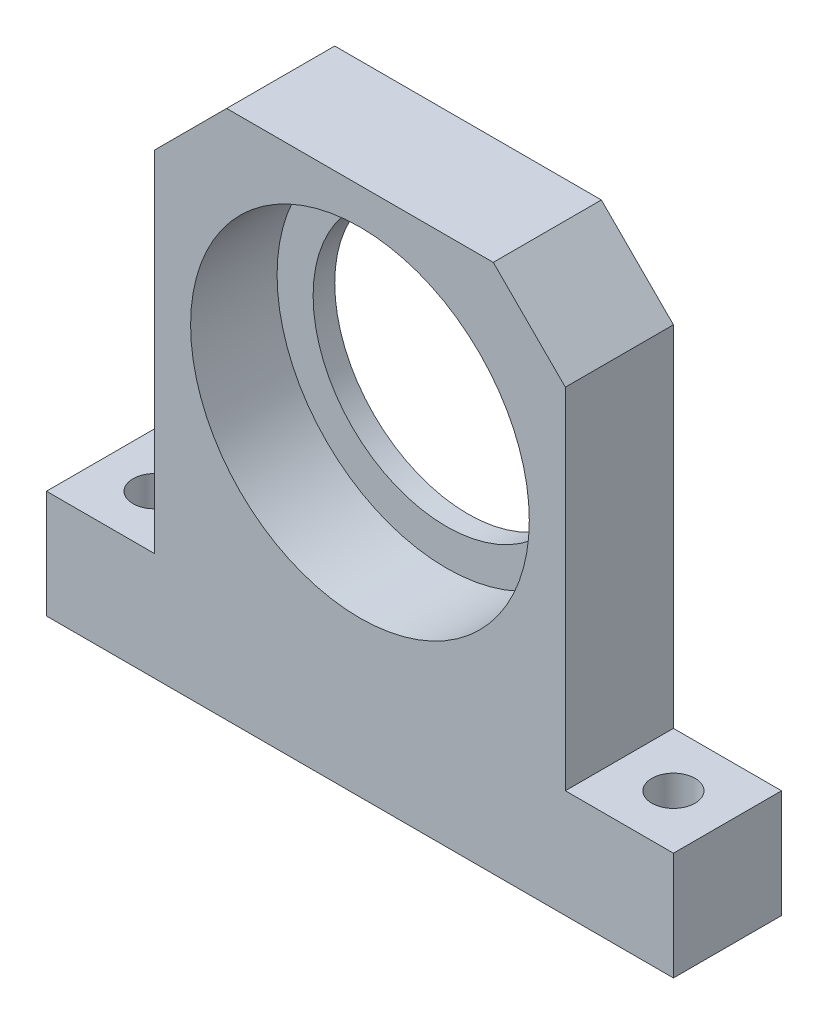
SolidWorks part; units mm, degrees
material "1060 合金"
ref_plane "前视" through (0, 0, 0) normal (0, 0, 1) x (1, 0, 0)
ref_plane "上视" through (0, 0, 0) normal (0, 1, 0) x (1, 0, 0)
ref_plane "右视" through (0, 0, 0) normal (1, 0, 0) x (0, 0, -1)
sketch "草图1" plane through (0, 0, 0) normal (0, 0, 1) x (1, 0, 0)
  line L0 (-28.5, 18.5) -> (-28.5, -30)
  line L1 (-28.5, -30) -> (-43.5, -30)
  line L2 (-43.5, -30) -> (-43.5, -45)
  line L3 (-43.5, -45) -> (43.5, -45)
  line L4 (43.5, -45) -> (43.5, -30)
  line L5 (43.5, -30) -> (28.5, -30)
  line L6 (28.5, -30) -> (28.5, 18.5)
  line L7 (18.5, 28.5) -> (-18.5, 28.5)
  line L8 (-18.5, 28.5) -> (-28.5, 18.5)
  line L9 (28.5, 18.5) -> (18.5, 28.5)
  circle A0 centre (0, 0) radius 23.5
  circle A1 centre (0, 0) radius 18.5
  point P10 (28.5, 28.5)
  point P11 (-28.5, 28.5)
  dimension "D1" = 47
  dimension "D14" = 5
  dimension "D2" = 28.5
  dimension "D3" = 28.5
  dimension "D4" = 28.5
  dimension "D5" = 45
  dimension "D6" = 15
  dimension "D7" = 15
  dimension "D8" = 15
  dimension "D9" = 15
  dimension "D10" = 10
  dimension "D11" = 10
  dimension "D12" = 10
  dimension "D13" = 10
extrude "凸台-拉伸1" add sketch "草图1" along normal blind 15 contours L6 L9 L7 L8 L0 L1 L2 L3 L4 L5 A0 region at (-22.6947, 22.6947, 0)
extrude "凸台-拉伸2" add sketch "草图1<3>" along normal blind 3 contours A0 A1 region at (-22.8353, 0, 0)
sketch "草图1<3>" plane through (0, 0, 0) normal (0, 0, 1) x (1, 0, 0) same geometry as "草图1"
sketch "草图2" plane through (0, -30, 0) normal (0, 1, 0) x (1, 0, 0)
  line L0 (-28.5, 0) -> (-43.5, 0) construction
  line L2 (-43.5, -15) -> (-43.5, 0) construction
  circle A0 centre (-36, -7.5) radius 3
  dimension "D1" = 6
  dimension "D2" = 7.5
  dimension "D3" = 7.5
extrude "切除-拉伸1" cut sketch "草图2" against normal through all
mirror "镜向1" about plane through (0, 0, 0) normal (1, 0, 0) of "切除-拉伸1"
